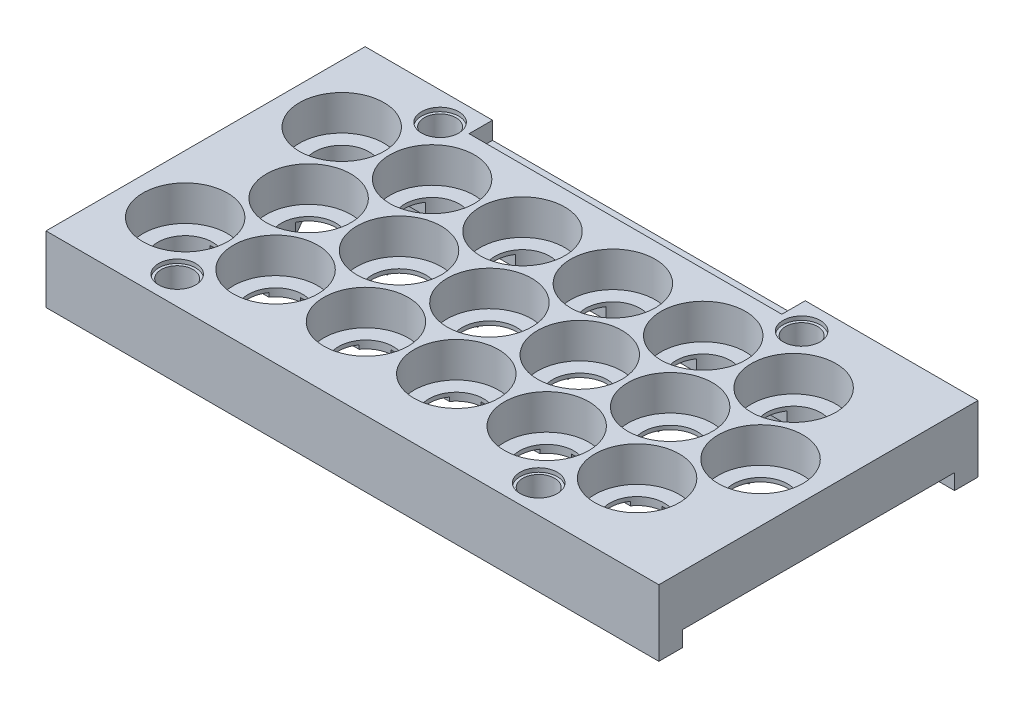
SolidWorks part; units mm, degrees
ref_plane "Front Plane" through (0, 0, 0) normal (0, 0, 1) x (1, 0, 0)
ref_plane "Top Plane" through (0, 0, 0) normal (0, 1, 0) x (1, 0, 0)
ref_plane "Right Plane" through (0, 0, 0) normal (1, 0, 0) x (0, 0, -1)
sketch "Sketch1" plane through (0, 0, 0) normal (0, 1, 0) x (1, 0, 0)
  line L0 (0, 0) -> (11.575, -20.0485) construction
  line L1 (11.575, -20.0485) -> (0, -40.097) construction
  line L2 (0, 0) -> (11.575, 0) construction
  line L3 (11.575, 0) -> (11.575, -20.0485) construction
  line L4 (11.575, -20.0485) -> (11.575, -40.097) construction
  line L5 (11.575, -40.097) -> (0, -40.097) construction
  line L6 (0, 0) -> (23.15, 0) construction
  line L7 (0, 0) -> (23.15, 0) construction
  line L8 (-14.825, -60.922) -> (142.15, -60.922)
  line L9 (-14.825, -60.922) -> (-14.825, 20.825)
  line L10 (-14.825, 20.825) -> (142.15, 20.825)
  line L11 (142.15, -60.922) -> (142.15, 20.825)
  circle A0 centre (0, 0) radius 10.825
  circle A1 centre (11.575, -20.0485) radius 10.825
  circle A2 centre (0, -40.097) radius 10.825
  circle A3 centre (23.15, 0) radius 10.825
  circle A4 centre (34.725, -20.0485) radius 10.825
  circle A5 centre (23.15, -40.097) radius 10.825
  circle A6 centre (46.3, 0) radius 10.825
  circle A7 centre (57.875, -20.0485) radius 10.825
  circle A8 centre (46.3, -40.097) radius 10.825
  circle A9 centre (69.45, 0) radius 10.825
  circle A10 centre (81.025, -20.0485) radius 10.825
  circle A11 centre (69.45, -40.097) radius 10.825
  circle A12 centre (92.6, 0) radius 10.825
  circle A13 centre (104.175, -20.0485) radius 10.825
  circle A14 centre (92.6, -40.097) radius 10.825
  circle A15 centre (115.75, 0) radius 10.825
  circle A16 centre (127.325, -20.0485) radius 10.825
  circle A17 centre (115.75, -40.097) radius 10.825
  circle A18 centre (0, 0) radius 7
  circle A19 centre (11.575, -20.0485) radius 7
  circle A20 centre (0, -40.097) radius 7
  circle A21 centre (23.15, 0) radius 7
  circle A22 centre (34.725, -20.0485) radius 7
  circle A23 centre (23.15, -40.097) radius 7
  circle A24 centre (46.3, 0) radius 7
  circle A25 centre (57.875, -20.0485) radius 7
  circle A26 centre (46.3, -40.097) radius 7
  circle A27 centre (69.45, 0) radius 7
  circle A28 centre (81.025, -20.0485) radius 7
  circle A29 centre (69.45, -40.097) radius 7
  circle A30 centre (92.6, 0) radius 7
  circle A31 centre (104.175, -20.0485) radius 7
  circle A32 centre (92.6, -40.097) radius 7
  circle A33 centre (115.75, 0) radius 7
  circle A34 centre (127.325, -20.0485) radius 7
  circle A35 centre (115.75, -40.097) radius 7
  dimension "D3" = 21.65
  dimension "D11" = 14
  dimension "D1" = 60
  dimension "D2" = 60
  dimension "D4" = 1.5
  dimension "D6" = 23.15
  dimension "D7" = 4
  dimension "D8" = 4
  dimension "D9" = 10
  dimension "D10" = 10
  dimension "D13" = 23.15
  dimension "D5" = 6
  dimension "D12" = 6
extrude "Boss-Extrude2" add sketch "Sketch1" along normal blind 11 contours L8 L11 L10 L9 A17 A16 A15 A14 A13 A12 A11 A10 A9 A8 A7 A6 A5 A4 A3 A2 A1 A0 region at (-13.0551, 0, 20.0485)
extrude "Boss-Extrude3" add sketch "Sketch1<3>" along normal blind 2 contours A0 A18 | A3 A21 | A6 A24 | A9 A27 | A12 A30 | A15 A33 | A1 A19 | A4 A22 | A7 A25 | A10 A28 | A13 A31 | A16 A34 | A17 A35 | A14 A32 | A11 A29 | A8 A26 | A5 A23 | A2 A20 region at (-10.5188, 0, 0) region at (1.0562, 0, 20.0485) region at (-10.5188, 0, 40.097) region at (12.6312, 0, 0) region at (24.2062, 0, 20.0485) region at (12.6312, 0, 40.097) region at (35.7812, 0, 0) region at (47.3562, 0, 20.0485) region at (35.7812, 0, 40.097) region at (58.9312, 0, 0) region at (70.5062, 0, 20.0485) region at (58.9312, 0, 40.097) region at (82.0812, 0, 0) region at (93.6562, 0, 20.0485) region at (82.0812, 0, 40.097) region at (105.2312, 0, 0) region at (116.8062, 0, 20.0485) region at (105.2312, 0, 40.097)
sketch "Sketch1<3>" plane through (0, 0, 0) normal (0, 1, 0) x (1, 0, 0) same geometry as "Sketch1"
sketch "Sketch2" plane through (0, 0, 0) normal (0, -1, 0) x (1, 0, 0)
  line L0 (0, 40.097) -> (11.575, 20.0485) construction
  line L1 (3.4641, 42.097) -> (15.0391, 22.0485)
  line L2 (-3.4641, 38.097) -> (8.1109, 18.0485)
  line L3 (11.575, 20.0485) -> (0, 0) construction
  line L4 (15.0391, 18.0485) -> (3.4641, -2)
  line L5 (8.1109, 22.0485) -> (-3.4641, 2)
  line L6 (19.6859, 38.097) -> (31.2609, 18.0485)
  line L7 (26.6141, 42.097) -> (38.1891, 22.0485)
  line L8 (31.2609, 22.0485) -> (19.6859, 2)
  line L9 (38.1891, 18.0485) -> (26.6141, -2)
  line L10 (23.15, 40.097) -> (34.725, 20.0485) construction
  line L11 (34.725, 20.0485) -> (23.15, 0) construction
  line L12 (42.8359, 38.097) -> (54.4109, 18.0485)
  line L13 (49.7641, 42.097) -> (61.3391, 22.0485)
  line L14 (54.4109, 22.0485) -> (42.8359, 2)
  line L15 (61.3391, 18.0485) -> (49.7641, -2)
  line L16 (46.3, 40.097) -> (57.875, 20.0485) construction
  line L17 (57.875, 20.0485) -> (46.3, 0) construction
  line L18 (65.9859, 38.097) -> (77.5609, 18.0485)
  line L19 (72.9141, 42.097) -> (84.4891, 22.0485)
  line L20 (77.5609, 22.0485) -> (65.9859, 2)
  line L21 (84.4891, 18.0485) -> (72.9141, -2)
  line L22 (69.45, 40.097) -> (81.025, 20.0485) construction
  line L23 (81.025, 20.0485) -> (69.45, 0) construction
  line L24 (89.1359, 38.097) -> (100.7109, 18.0485)
  line L25 (96.0641, 42.097) -> (107.6391, 22.0485)
  line L26 (100.7109, 22.0485) -> (89.1359, 2)
  line L27 (107.6391, 18.0485) -> (96.0641, -2)
  line L28 (92.6, 40.097) -> (104.175, 20.0485) construction
  line L29 (104.175, 20.0485) -> (92.6, 0) construction
  line L30 (112.2859, 38.097) -> (123.8609, 18.0485)
  line L31 (119.2141, 42.097) -> (130.7891, 22.0485)
  line L32 (123.8609, 22.0485) -> (112.2859, 2)
  line L33 (130.7891, 18.0485) -> (119.2141, -2)
  line L34 (115.75, 40.097) -> (127.325, 20.0485) construction
  line L35 (127.325, 20.0485) -> (115.75, 0) construction
  line L36 (-3.4641, 38.097) -> (19.6859, 38.097) construction
  line L37 (0, 40.097) -> (115.75, 40.097) construction
  line L38 (0, 44.097) -> (115.75, 44.097)
  line L39 (0, 36.097) -> (115.75, 36.097)
  line L40 (11.575, 20.0485) -> (127.325, 20.0485) construction
  line L41 (11.575, 24.0485) -> (127.325, 24.0485)
  line L42 (11.575, 16.0485) -> (127.325, 16.0485)
  line L43 (0, 0) -> (115.75, 0) construction
  line L44 (0, 4) -> (115.75, 4)
  line L45 (0, -4) -> (115.75, -4)
  arc A0 (3.4641, 42.097) -> (-3.4641, 38.097) centre (0, 40.097) ccw
  arc A1 (8.1109, 18.0485) -> (15.0391, 22.0485) centre (11.575, 20.0485) ccw
  arc A2 (15.0391, 18.0485) -> (8.1109, 22.0485) centre (11.575, 20.0485) ccw
  arc A3 (-3.4641, 2) -> (3.4641, -2) centre (0, 0) ccw
  arc A4 (26.6141, 42.097) -> (19.6859, 38.097) centre (23.15, 40.097) ccw
  arc A5 (31.2609, 18.0485) -> (38.1891, 22.0485) centre (34.725, 20.0485) ccw
  arc A6 (38.1891, 18.0485) -> (31.2609, 22.0485) centre (34.725, 20.0485) ccw
  arc A7 (19.6859, 2) -> (26.6141, -2) centre (23.15, 0) ccw
  arc A8 (49.7641, 42.097) -> (42.8359, 38.097) centre (46.3, 40.097) ccw
  arc A9 (54.4109, 18.0485) -> (61.3391, 22.0485) centre (57.875, 20.0485) ccw
  arc A10 (61.3391, 18.0485) -> (54.4109, 22.0485) centre (57.875, 20.0485) ccw
  arc A11 (42.8359, 2) -> (49.7641, -2) centre (46.3, 0) ccw
  arc A12 (72.9141, 42.097) -> (65.9859, 38.097) centre (69.45, 40.097) ccw
  arc A13 (77.5609, 18.0485) -> (84.4891, 22.0485) centre (81.025, 20.0485) ccw
  arc A14 (84.4891, 18.0485) -> (77.5609, 22.0485) centre (81.025, 20.0485) ccw
  arc A15 (65.9859, 2) -> (72.9141, -2) centre (69.45, 0) ccw
  arc A16 (96.0641, 42.097) -> (89.1359, 38.097) centre (92.6, 40.097) ccw
  arc A17 (100.7109, 18.0485) -> (107.6391, 22.0485) centre (104.175, 20.0485) ccw
  arc A18 (107.6391, 18.0485) -> (100.7109, 22.0485) centre (104.175, 20.0485) ccw
  arc A19 (89.1359, 2) -> (96.0641, -2) centre (92.6, 0) ccw
  arc A20 (119.2141, 42.097) -> (112.2859, 38.097) centre (115.75, 40.097) ccw
  arc A21 (123.8609, 18.0485) -> (130.7891, 22.0485) centre (127.325, 20.0485) ccw
  arc A22 (130.7891, 18.0485) -> (123.8609, 22.0485) centre (127.325, 20.0485) ccw
  arc A23 (112.2859, 2) -> (119.2141, -2) centre (115.75, 0) ccw
  arc A24 (0, 44.097) -> (0, 36.097) centre (0, 40.097) ccw
  arc A25 (115.75, 36.097) -> (115.75, 44.097) centre (115.75, 40.097) ccw
  arc A26 (11.575, 24.0485) -> (11.575, 16.0485) centre (11.575, 20.0485) ccw
  arc A27 (127.325, 16.0485) -> (127.325, 24.0485) centre (127.325, 20.0485) ccw
  arc A28 (0, 4) -> (0, -4) centre (0, 0) ccw
  arc A29 (115.75, -4) -> (115.75, 4) centre (115.75, 0) ccw
  point P3 (5.7875, 30.0727)
  point P8 (5.7875, 10.0242)
  point P18 (28.9375, 30.0727)
  point P25 (28.9375, 10.0242)
  point P34 (52.0875, 30.0727)
  point P39 (52.0875, 10.0242)
  point P48 (75.2375, 30.0727)
  point P53 (75.2375, 10.0242)
  point P62 (98.3875, 30.0727)
  point P67 (98.3875, 10.0242)
  point P76 (121.5375, 30.0727)
  point P81 (121.5375, 10.0242)
  point P91 (57.875, 40.097)
  point P96 (69.45, 20.0485)
  point P103 (57.875, 0)
  circle M62 centre (0, 0) radius 7
  circle M63 centre (23.15, 0) radius 7
  circle M64 centre (46.3, 0) radius 7
  circle M65 centre (69.45, 0) radius 7
  circle M66 centre (92.6, 0) radius 7
  circle M67 centre (115.75, 0) radius 7
  circle M68 centre (11.575, 20.0485) radius 7
  circle M69 centre (34.725, 20.0485) radius 7
  circle M70 centre (57.875, 20.0485) radius 7
  circle M71 centre (81.025, 20.0485) radius 7
  circle M72 centre (104.175, 20.0485) radius 7
  circle M73 centre (127.325, 20.0485) radius 7
  circle M74 centre (115.75, 40.097) radius 7
  circle M75 centre (92.6, 40.097) radius 7
  circle M76 centre (69.45, 40.097) radius 7
  circle M77 centre (46.3, 40.097) radius 7
  circle M78 centre (23.15, 40.097) radius 7
  circle M79 centre (0, 40.097) radius 7
  dimension "D1" = 8
  dimension "D3" = 23.15
  dimension "D4" = 8
  dimension "D5" = 8
  dimension "D6" = 8
extrude "Cut-Extrude1" cut sketch "Sketch2" against normal blind 1 contours L1 L39 L38 M78 M79 | L7 L39 L38 M77 M78 | L39 L2 L1 M79 M68 | L42 L8 L6 L41 M68 M69 | L6 L41 L7 L39 M69 M78 | L12 L41 L13 L39 M70 M77 | L13 L39 L38 M76 M77 | L18 L41 L19 L39 M71 M76 | L19 L39 L38 M75 M76 | L24 L41 L25 L39 M72 M75 | L25 L39 L38 M74 M75 | L30 L41 L31 M73 M74 | L42 L32 L30 L41 M72 M73 | L42 L26 L24 L41 M71 M72 | L42 L20 L18 L41 M70 M71 | L42 L14 L12 L41 M69 M70 | L45 L44 L4 M62 M63 | L44 L4 L5 M62 M68 | L45 L44 L9 M63 M64 | L45 L44 L15 M64 M65 | L45 L44 L21 M65 M66 | L45 L44 L27 M66 M67 | L44 L27 L42 L26 M66 M72 | L42 L32 L33 M67 M73 | L44 L21 L42 L20 M65 M71 | L44 L15 L42 L14 M64 M70 | L39 L13 M77 | L39 L25 M75 | L39 L19 M76 | L41 L6 M69 | L44 L4 M62 | L44 L15 M64 | L44 L21 M65 | L44 L27 M66 | L41 L30 M73 | L32 L42 M73 | L41 L24 M72 | L26 L42 M72 | L41 L18 M71 | L20 L42 M71 | L41 L12 M70 | L14 L42 M70 | L44 L9 L42 L8 M63 M69 | L8 L42 M69 | L39 L7 M78 | L39 L1 M79 | L44 A29 L45 A28 region at (11.6138, 0, 40.1242) region at (6.3461, 0, 36.4331) region at (5.7834, 0, 30.0255) region at (23.0718, 0, 20.0485) region at (28.9375, 0, 30.0727) region at (34.7638, 0, 40.1242) region at (28.3789, 0, 23.7124) region at (5.7834, 0, 10.0715) region at (29.4961, 0, 36.4331) region at (57.9138, 0, 40.1242) region at (28.3789, 0, 16.3846) region at (28.9375, 0, 10.0242) region at (6.3461, 0, 3.6639) region at (11.6138, 0, -0.0272) region at (52.0875, 0, 30.0727) region at (46.2218, 0, 20.0485) region at (52.6461, 0, 36.4331) region at (81.0638, 0, 40.1242) region at (51.5289, 0, 23.7124) region at (34.7638, 0, -0.0272) region at (75.2375, 0, 30.0727) region at (75.7961, 0, 36.4331) region at (104.2138, 0, 40.1242) region at (74.6789, 0, 23.7124) region at (69.3718, 0, 20.0485) region at (51.5289, 0, 16.3846) region at (52.0875, 0, 10.0242) region at (57.9138, 0, -0.0272) region at (98.3875, 0, 30.0727) region at (98.9461, 0, 36.4331) region at (97.8289, 0, 23.7124) region at (92.5218, 0, 20.0485) region at (74.6789, 0, 16.3846) region at (52.6461, 0, 3.6639) region at (81.0638, 0, -0.0272) region at (121.5416, 0, 30.12) region at (75.2375, 0, 10.0242) region at (120.9789, 0, 23.7124) region at (115.6718, 0, 20.0485) region at (97.8289, 0, 16.3846) region at (75.7961, 0, 3.6639) region at (104.2138, 0, -0.0272) region at (98.3875, 0, 10.0242) region at (121.5416, 0, 9.977) region at (120.9789, 0, 16.3846) region at (98.9461, 0, 3.6639)
sketch "Sketch9" plane through (0, 11, 0) normal (0, 1, 0) x (1, 0, 0)
  line L0 (11.575, -60.922) -> (11.575, 20.825)
  line L1 (-14.825, 20.825) -> (142.15, 20.825) construction
  line L2 (104.175, 20.825) -> (104.175, -60.922)
  line L3 (-14.825, -60.922) -> (142.15, -60.922) construction
  circle A0 centre (11.575, 13.625) radius 4.0767
  circle A1 centre (11.575, -53.722) radius 4.0767
  circle A2 centre (104.175, -53.722) radius 4.0767
  circle A3 centre (104.175, 13.625) radius 4.0767
  point P0 (11.575, 13.625)
  point P7 (11.575, -20.0485)
  point P15 (104.175, -20.0485)
  point P20 (104.175, 13.625)
  point P21 (104.175, -53.722)
  point P22 (11.575, -53.722)
  dimension "D5" = 8.1534
  dimension "D1" = 7.2
  dimension "D4" = 7.2
extrude "Cut-Extrude3" cut sketch "Sketch9" against normal up to next contours A2 | A1 | A0 | A3
sketch "Sketch10" plane through (0, 11, 0) normal (0, 1, 0) x (1, 0, 0)
  circle A0 centre (11.575, 13.625) radius 4.7625
  circle A1 centre (104.175, 13.625) radius 4.7625
  circle A2 centre (104.175, -53.722) radius 4.7625
  circle A3 centre (11.575, -53.722) radius 4.7625
  dimension "D1" = 9.525
extrude "Cut-Extrude4" cut sketch "Sketch10" against normal blind 1
sketch "Sketch13" plane through (0, 0, 0) normal (0, -1, 0) x (1, 0, 0)
  line L0 (142.15, 60.922) -> (142.15, -20.825) construction
  line L5 (3.575, 53.722) -> (3.575, 60.922)
  line L8 (-14.825, 60.922) -> (142.15, 60.922) construction
  line L9 (3.575, 60.922) -> (19.575, 60.922)
  line L10 (19.575, 60.922) -> (19.575, 53.722)
  line L12 (57.875, 20.0485) -> (57.875, -20.825) construction
  line L13 (-14.825, -20.825) -> (142.15, -20.825) construction
  line L14 (11.575, 20.0485) -> (127.325, 20.0485) construction
  line L16 (96.175, 60.922) -> (96.175, 53.722)
  line L17 (112.175, 60.922) -> (96.175, 60.922)
  line L18 (112.175, 53.722) -> (112.175, 60.922)
  line L19 (-14.825, 60.922) -> (142.15, 60.922)
  line L20 (-14.825, 60.922) -> (-14.825, 54.922)
  line L21 (-14.825, 54.922) -> (142.15, 54.922)
  line L22 (142.15, 60.922) -> (142.15, 54.922)
  line L23 (142.15, -20.825) -> (142.15, -14.825)
  line L24 (-14.825, -14.825) -> (142.15, -14.825)
  line L25 (-14.825, -20.825) -> (-14.825, -14.825)
  line L26 (-14.825, -20.825) -> (142.15, -20.825)
  line L27 (112.175, -13.625) -> (112.175, -20.825)
  line L28 (112.175, -20.825) -> (96.175, -20.825)
  line L29 (96.175, -20.825) -> (96.175, -13.625)
  line L32 (19.575, -20.825) -> (19.575, -13.625)
  line L33 (3.575, -20.825) -> (19.575, -20.825)
  line L34 (3.575, -13.625) -> (3.575, -20.825)
  circle A4 centre (11.575, 53.722) radius 6.5
  circle A5 centre (11.575, 53.722) radius 8
  circle A6 centre (104.175, 53.722) radius 8
  circle A7 centre (104.175, 53.722) radius 6.5
  circle A8 centre (104.175, -13.625) radius 6.5
  circle A9 centre (104.175, -13.625) radius 8
  circle A10 centre (11.575, -13.625) radius 8
  circle A11 centre (11.575, -13.625) radius 6.5
  line M15 (142.15, 60.922) -> (-14.825, 60.922)
  line M16 (-14.825, 60.922) -> (-14.825, -20.825)
  line M17 (-14.825, -20.825) -> (142.15, -20.825)
  line M18 (142.15, -20.825) -> (142.15, 60.922)
  dimension "D1" = 13
  dimension "D2" = 16
  dimension "D3" = 6
extrude "Boss-Extrude7" add sketch "Sketch13" along normal blind 6 contours L21 L5 M16 M15 | A5 L5 L21 M15 | A5 L21 L10 M15 | L10 L21 L16 M15 | L21 A5 L19 A4 | A5 L21 A4 | L21 A6 L16 M15 | L21 A7 A6 L19 | L21 A7 A6 | A6 L21 L18 M15 | L18 L21 M18 M15 | A9 L24 L29 L26 | L28 A9 L24 A8 | A9 L26 L27 L24 | L24 L27 L26 M18 | L32 L26 L29 L24 | L24 A9 A8 | L34 L24 M16 M17 | L26 A10 L24 L34 | L24 A11 A10 | L24 A11 A10 L33 | L24 A10 L26 L32 region at (3.7817, 0, 54.3098) region at (-5.625, 0, 57.922) region at (4.8282, 0, 59.2567) region at (5.2714, 0, 58.3681) region at (18.3218, 0, 59.2567) region at (57.875, 0, 57.922) region at (-5.625, 0, -17.825) region at (97.4282, 0, 59.2567) region at (4.8282, 0, -19.1597) region at (96.3817, 0, 54.3098) region at (97.8714, 0, 58.3681) region at (3.7817, 0, -14.2128) region at (4.4261, 0, -14.9942) region at (110.9218, 0, 59.2567) region at (127.1625, 0, 57.922) region at (18.3218, 0, -19.1597) region at (57.875, 0, -17.825) region at (97.4282, 0, -19.1597) region at (127.1625, 0, -17.825) region at (96.3817, 0, -14.2128) region at (97.0261, 0, -14.9942) region at (110.9218, 0, -19.1597)
sketch "Sketch14" plane through (0, 0, 0) normal (0, -1, 0) x (1, 0, 0)
  line L2 (142.15, 54.922) -> (142.15, -14.825) construction
  line L4 (5.2386, 17.0736) -> (-0.5918, 6.9749) construction
  line L5 (5.7446, -4) -> (17.4054, -4) construction
  line L6 (28.8946, -4) -> (40.5554, -4) construction
  line L7 (52.0446, -4) -> (63.7054, -4) construction
  line L8 (75.1946, -4) -> (86.8554, -4) construction
  line L9 (98.3446, -4) -> (110.0054, -4) construction
  line L10 (127.9168, 13.0736) -> (122.0864, 2.9749) construction
  line L11 (122.0864, 37.122) -> (127.9168, 27.0234) construction
  line L12 (98.3446, 44.097) -> (110.0054, 44.097) construction
  line L13 (75.1946, 44.097) -> (86.8554, 44.097) construction
  line L14 (52.0446, 44.097) -> (63.7054, 44.097) construction
  line L15 (28.8946, 44.097) -> (40.5554, 44.097) construction
  line L16 (-0.5918, 33.122) -> (5.2386, 23.0234) construction
  line L17 (5.7446, 44.097) -> (17.4054, 44.097) construction
  line L20 (142.15, 54.922) -> (142.15, -14.825)
  line L22 (5.2386, 17.0736) -> (-0.5918, 6.9749)
  line L23 (5.7446, -4) -> (17.4054, -4)
  line L24 (28.8946, -4) -> (40.5554, -4)
  line L25 (52.0446, -4) -> (63.7054, -4)
  line L26 (75.1946, -4) -> (86.8554, -4)
  line L27 (98.3446, -4) -> (110.0054, -4)
  line L28 (127.9168, 13.0736) -> (122.0864, 2.9749)
  line L29 (122.0864, 37.122) -> (127.9168, 27.0234)
  line L30 (98.3446, 44.097) -> (110.0054, 44.097)
  line L31 (75.1946, 44.097) -> (86.8554, 44.097)
  line L32 (52.0446, 44.097) -> (63.7054, 44.097)
  line L33 (28.8946, 44.097) -> (40.5554, 44.097)
  line L34 (-0.5918, 33.122) -> (5.2386, 23.0234)
  line L35 (5.7446, 44.097) -> (17.4054, 44.097)
  line L36 (112.0845, -14.825) -> (142.15, -14.825) construction
  line L37 (19.4845, -14.825) -> (96.2655, -14.825) construction
  line L38 (-14.825, -14.825) -> (3.6655, -14.825) construction
  line L39 (-14.825, 54.922) -> (-14.825, -14.825) construction
  line L40 (112.0845, 54.922) -> (142.15, 54.922) construction
  line L41 (19.4845, 54.922) -> (96.2655, 54.922) construction
  line L42 (-14.825, 54.922) -> (3.6655, 54.922) construction
  line L43 (112.0845, -14.825) -> (142.15, -14.825)
  line L44 (19.4845, -14.825) -> (96.2655, -14.825)
  line L45 (-14.825, -14.825) -> (3.6655, -14.825)
  line L46 (-14.825, 54.922) -> (-14.825, -14.825)
  line L47 (112.0845, 54.922) -> (142.15, 54.922)
  line L48 (19.4845, 54.922) -> (96.2655, 54.922)
  line L49 (-14.825, 54.922) -> (3.6655, 54.922)
  arc A3 (5.2386, 23.0234) -> (5.2386, 17.0736) centre (11.575, 20.0485) ccw construction
  arc A4 (-0.5918, 6.9749) -> (5.7446, -4) centre (0, 0) ccw construction
  arc A5 (17.4054, -4) -> (28.8946, -4) centre (23.15, 0) ccw construction
  arc A6 (40.5554, -4) -> (52.0446, -4) centre (46.3, 0) ccw construction
  arc A7 (63.7054, -4) -> (75.1946, -4) centre (69.45, 0) ccw construction
  arc A8 (86.8554, -4) -> (98.3446, -4) centre (92.6, 0) ccw construction
  arc A9 (110.0054, -4) -> (122.0864, 2.9749) centre (115.75, 0) ccw construction
  arc A10 (127.9168, 13.0736) -> (127.9168, 27.0234) centre (127.325, 20.0485) ccw construction
  arc A11 (122.0864, 37.122) -> (110.0054, 44.097) centre (115.75, 40.097) ccw construction
  arc A12 (98.3446, 44.097) -> (86.8554, 44.097) centre (92.6, 40.097) ccw construction
  arc A13 (75.1946, 44.097) -> (63.7054, 44.097) centre (69.45, 40.097) ccw construction
  arc A14 (52.0446, 44.097) -> (40.5554, 44.097) centre (46.3, 40.097) ccw construction
  arc A16 (28.8946, 44.097) -> (17.4054, 44.097) centre (23.15, 40.097) ccw construction
  arc A17 (5.7446, 44.097) -> (-0.5918, 33.122) centre (0, 40.097) ccw construction
  arc A21 (5.2386, 23.0234) -> (5.2386, 17.0736) centre (11.575, 20.0485) ccw
  arc A22 (-0.5918, 6.9749) -> (5.7446, -4) centre (0, 0) ccw
  arc A23 (17.4054, -4) -> (28.8946, -4) centre (23.15, 0) ccw
  arc A24 (40.5554, -4) -> (52.0446, -4) centre (46.3, 0) ccw
  arc A25 (63.7054, -4) -> (75.1946, -4) centre (69.45, 0) ccw
  arc A26 (86.8554, -4) -> (98.3446, -4) centre (92.6, 0) ccw
  arc A27 (110.0054, -4) -> (122.0864, 2.9749) centre (115.75, 0) ccw
  arc A28 (127.9168, 13.0736) -> (127.9168, 27.0234) centre (127.325, 20.0485) ccw
  arc A29 (122.0864, 37.122) -> (110.0054, 44.097) centre (115.75, 40.097) ccw
  arc A30 (98.3446, 44.097) -> (86.8554, 44.097) centre (92.6, 40.097) ccw
  arc A31 (75.1946, 44.097) -> (63.7054, 44.097) centre (69.45, 40.097) ccw
  arc A32 (52.0446, 44.097) -> (40.5554, 44.097) centre (46.3, 40.097) ccw
  arc A34 (28.8946, 44.097) -> (17.4054, 44.097) centre (23.15, 40.097) ccw
  arc A35 (5.7446, 44.097) -> (-0.5918, 33.122) centre (0, 40.097) ccw
  arc A36 (112.0845, -14.825) -> (96.2655, -14.825) centre (104.175, -13.625) ccw construction
  arc A37 (19.4845, -14.825) -> (3.6655, -14.825) centre (11.575, -13.625) ccw construction
  arc A38 (96.2655, 54.922) -> (112.0845, 54.922) centre (104.175, 53.722) ccw construction
  arc A39 (3.6655, 54.922) -> (19.4845, 54.922) centre (11.575, 53.722) ccw construction
  arc A40 (112.0845, -14.825) -> (96.2655, -14.825) centre (104.175, -13.625) ccw
  arc A41 (19.4845, -14.825) -> (3.6655, -14.825) centre (11.575, -13.625) ccw
  arc A42 (96.2655, 54.922) -> (112.0845, 54.922) centre (104.175, 53.722) ccw
  arc A43 (3.6655, 54.922) -> (19.4845, 54.922) centre (11.575, 53.722) ccw
extrude "Boss-Extrude9" add sketch "Sketch14" along normal blind 2
sketch "Sketch16" plane through (0, 0, 0) normal (0, -1, 0) x (1, 0, 0)
  line L0 (17.4054, 36.097) -> (12.1668, 27.0234) construction
  line L1 (12.1668, 27.0234) -> (17.3196, 24.0485) construction
  line L2 (17.3196, 24.0485) -> (22.5582, 33.122) construction
  line L3 (22.5582, 33.122) -> (17.4054, 36.097) construction
  line L4 (14.7861, 31.5602) -> (19.9389, 28.5853) construction
  line L5 (15.5361, 32.8592) -> (20.6889, 29.8843)
  line L6 (14.0361, 30.2612) -> (19.1889, 27.2862)
  line L7 (11.575, 20.0485) -> (126.446, 20.0485) construction
  line L8 (40.5554, 36.097) -> (35.3168, 27.0234) construction
  line L9 (35.3168, 27.0234) -> (40.4696, 24.0485) construction
  line L10 (40.4696, 24.0485) -> (45.7082, 33.122) construction
  line L11 (45.7082, 33.122) -> (40.5554, 36.097) construction
  line L12 (37.9361, 31.5602) -> (43.0889, 28.5853) construction
  line L13 (38.6861, 32.8592) -> (43.8389, 29.8843)
  line L14 (37.1861, 30.2612) -> (42.3389, 27.2862)
  line L15 (63.7054, 36.097) -> (58.4668, 27.0234) construction
  line L16 (58.4668, 27.0234) -> (63.6196, 24.0485) construction
  line L17 (63.6196, 24.0485) -> (68.8582, 33.122) construction
  line L18 (68.8582, 33.122) -> (63.7054, 36.097) construction
  line L19 (61.0861, 31.5602) -> (66.2389, 28.5853) construction
  line L20 (61.8361, 32.8592) -> (66.9889, 29.8843)
  line L21 (60.3361, 30.2612) -> (65.4889, 27.2862)
  line L22 (86.8554, 36.097) -> (81.6168, 27.0234) construction
  line L23 (81.6168, 27.0234) -> (86.7696, 24.0485) construction
  line L24 (86.7696, 24.0485) -> (92.0082, 33.122) construction
  line L25 (92.0082, 33.122) -> (86.8554, 36.097) construction
  line L26 (84.2361, 31.5602) -> (89.3889, 28.5853) construction
  line L27 (84.9861, 32.8592) -> (90.1389, 29.8843)
  line L28 (83.4861, 30.2612) -> (88.6389, 27.2862)
  line L29 (110.0054, 36.097) -> (104.7668, 27.0234) construction
  line L30 (104.7668, 27.0234) -> (109.9196, 24.0485) construction
  line L31 (109.9196, 24.0485) -> (115.1582, 33.122) construction
  line L32 (115.1582, 33.122) -> (110.0054, 36.097) construction
  line L33 (107.3861, 31.5602) -> (112.5389, 28.5853) construction
  line L34 (108.1361, 32.8592) -> (113.2889, 29.8843)
  line L35 (106.6361, 30.2612) -> (111.7889, 27.2862)
  line L36 (14.7861, 8.5368) -> (19.9389, 11.5117) construction
  line L37 (15.5361, 7.2377) -> (20.6889, 10.2127)
  line L38 (14.0361, 9.8358) -> (19.1889, 12.8108)
  line L39 (37.9361, 8.5368) -> (43.0889, 11.5117) construction
  line L40 (38.6861, 7.2377) -> (43.8389, 10.2127)
  line L41 (37.1861, 9.8358) -> (42.3389, 12.8108)
  line L42 (61.0861, 8.5368) -> (66.2389, 11.5117) construction
  line L43 (61.8361, 7.2377) -> (66.9889, 10.2127)
  line L44 (60.3361, 9.8358) -> (65.4889, 12.8108)
  line L45 (84.2361, 8.5368) -> (89.3889, 11.5117) construction
  line L46 (84.9861, 7.2377) -> (90.1389, 10.2127)
  line L47 (83.4861, 9.8358) -> (88.6389, 12.8108)
  line L48 (107.3861, 8.5368) -> (112.5389, 11.5117) construction
  line L49 (108.1361, 7.2377) -> (113.2889, 10.2127)
  line L50 (106.6361, 9.8358) -> (111.7889, 12.8108)
  line L51 (115.1582, 6.9749) -> (110.0054, 4) construction
  line L52 (109.9196, 16.0485) -> (115.1582, 6.9749) construction
  line L53 (104.7668, 13.0736) -> (109.9196, 16.0485) construction
  line L54 (110.0054, 4) -> (104.7668, 13.0736) construction
  line L55 (92.0082, 6.9749) -> (86.8554, 4) construction
  line L56 (86.7696, 16.0485) -> (92.0082, 6.9749) construction
  line L57 (81.6168, 13.0736) -> (86.7696, 16.0485) construction
  line L58 (86.8554, 4) -> (81.6168, 13.0736) construction
  line L59 (68.8582, 6.9749) -> (63.7054, 4) construction
  line L60 (63.6196, 16.0485) -> (68.8582, 6.9749) construction
  line L61 (58.4668, 13.0736) -> (63.6196, 16.0485) construction
  line L62 (63.7054, 4) -> (58.4668, 13.0736) construction
  line L63 (45.7082, 6.9749) -> (40.5554, 4) construction
  line L64 (40.4696, 16.0485) -> (45.7082, 6.9749) construction
  line L65 (35.3168, 13.0736) -> (40.4696, 16.0485) construction
  line L66 (40.5554, 4) -> (35.3168, 13.0736) construction
  line L67 (22.5582, 6.9749) -> (17.4054, 4) construction
  line L68 (17.3196, 16.0485) -> (22.5582, 6.9749) construction
  line L69 (12.1668, 13.0736) -> (17.3196, 16.0485) construction
  line L70 (17.4054, 4) -> (12.1668, 13.0736) construction
  arc A0 (15.5361, 32.8592) -> (14.0361, 30.2612) centre (14.7861, 31.5602) ccw
  arc A1 (19.1889, 27.2862) -> (20.6889, 29.8843) centre (19.9389, 28.5853) ccw
  arc A2 (38.6861, 32.8592) -> (37.1861, 30.2612) centre (37.9361, 31.5602) ccw
  arc A3 (42.3389, 27.2862) -> (43.8389, 29.8843) centre (43.0889, 28.5853) ccw
  arc A4 (61.8361, 32.8592) -> (60.3361, 30.2612) centre (61.0861, 31.5602) ccw
  arc A5 (65.4889, 27.2862) -> (66.9889, 29.8843) centre (66.2389, 28.5853) ccw
  arc A6 (84.9861, 32.8592) -> (83.4861, 30.2612) centre (84.2361, 31.5602) ccw
  arc A7 (88.6389, 27.2862) -> (90.1389, 29.8843) centre (89.3889, 28.5853) ccw
  arc A8 (108.1361, 32.8592) -> (106.6361, 30.2612) centre (107.3861, 31.5602) ccw
  arc A9 (111.7889, 27.2862) -> (113.2889, 29.8843) centre (112.5389, 28.5853) ccw
  arc A10 (40.5554, 36.097) -> (45.7082, 33.122) centre (46.3, 40.097) ccw construction
  arc A11 (15.5361, 7.2377) -> (14.0361, 9.8358) centre (14.7861, 8.5368) cw
  arc A12 (19.1889, 12.8108) -> (20.6889, 10.2127) centre (19.9389, 11.5117) cw
  arc A13 (38.6861, 7.2377) -> (37.1861, 9.8358) centre (37.9361, 8.5368) cw
  arc A14 (42.3389, 12.8108) -> (43.8389, 10.2127) centre (43.0889, 11.5117) cw
  arc A15 (61.8361, 7.2377) -> (60.3361, 9.8358) centre (61.0861, 8.5368) cw
  arc A16 (65.4889, 12.8108) -> (66.9889, 10.2127) centre (66.2389, 11.5117) cw
  arc A17 (84.9861, 7.2377) -> (83.4861, 9.8358) centre (84.2361, 8.5368) cw
  arc A18 (88.6389, 12.8108) -> (90.1389, 10.2127) centre (89.3889, 11.5117) cw
  arc A19 (108.1361, 7.2377) -> (106.6361, 9.8358) centre (107.3861, 8.5368) cw
  arc A20 (111.7889, 12.8108) -> (113.2889, 10.2127) centre (112.5389, 11.5117) cw
  point P10 (17.3625, 30.0727)
  point P25 (40.5125, 30.0727)
  point P36 (63.6625, 30.0727)
  point P47 (86.8125, 30.0727)
  point P58 (109.9625, 30.0727)
  point P68 (17.3625, 10.0242)
  point P75 (40.5125, 10.0242)
  point P82 (63.6625, 10.0242)
  point P89 (86.8125, 10.0242)
  point P96 (109.9625, 10.0242)
  dimension "D1" = 1.5
  dimension "D2" = 5
extrude "Boss-Extrude10" add sketch "Sketch16" along normal blind 2
sketch "Sketch17" plane through (0, -2, 0) normal (0, -1, 0) x (-1, 0, 0)
  line L0 (-57.875, -44.097) -> (-57.875, -54.922) construction
  line L1 (-63.7054, -44.097) -> (-52.0446, -44.097) construction
  line L2 (-19.4845, -54.922) -> (-96.2655, -54.922) construction
  line L3 (-142.15, 14.825) -> (-142.15, -54.922) construction
  line L4 (14.825, -54.922) -> (14.825, 14.825) construction
  line L5 (10.825, -49.5095) -> (-57.875, -49.5095) construction
  line L6 (-57.875, -49.5095) -> (-132.15, -49.5095) construction
  line L7 (-127.325, -20.0485) -> (-11.575, -20.0485)
  line L8 (-57.875, 9.4125) -> (-132.15, 9.4125) construction
  line L9 (10.825, 9.4125) -> (-57.875, 9.4125) construction
  line L10 (-57.875, 4) -> (-57.875, 14.825) construction
  circle A0 centre (10.825, -49.5095) radius 2
  circle A1 centre (-57.875, -49.5095) radius 2
  circle A2 centre (-132.15, -49.5095) radius 2
  circle A3 centre (-132.15, 9.4125) radius 2
  circle A4 centre (-57.875, 9.4125) radius 2
  circle A5 centre (10.825, 9.4125) radius 2
  dimension "D1" = 4
  dimension "D2" = 10
  dimension "D3" = 4
extrude "Cut-Extrude5" cut sketch "Sketch17" against normal blind 4 contours A3 | A2 | A4 | A5 | A0 | A1 region at (-10.825, -2, 49.5095) region at (57.875, -2, 49.5095) region at (132.15, -2, 49.5095) region at (132.15, -2, -9.4125) region at (57.875, -2, -9.4125) region at (-10.825, -2, -9.4125)
sketch "Sketch18" plane through (0, 0, -20.825) normal (0, 0, -1) x (-1, 0, 0)
  line L1 (-97.9, 11) -> (-17.8, 11)
  line L2 (-97.9, 11) -> (-17.8, 11)
  line L3 (-97.9, 11) -> (-97.9, 6.525)
  line L4 (-17.8, 11) -> (-17.8, 6.525)
  line L5 (-97.9, 6.525) -> (-17.8, 6.525)
  line L6 (-104.15, 11) -> (-11.55, 11)
  line L7 (14.825, 11) -> (-142.15, 11) construction
  point P0 (-87.2385, 11)
  point P7 (-57.85, 11)
  point P10 (-57.85, 11)
  line M8 (14.825, 11) -> (-142.15, 11)
  dimension "D1" = 80.1
  dimension "D2" = 4.475
  dimension "D3" = 92.6
  dimension "D4" = 38
extrude "Cut-Extrude6" cut sketch "Sketch18" against normal blind 6 contours L3 L5 L4 M8 region at (57.85, 8.7625, -20.825)
sketch "Sketch19" plane through (0, 0, -20.825) normal (0, 0, -1) x (-1, 0, 0)
  line L0 (-85.9, 6.525) -> (-29.8, 6.525)
  line L1 (-85.9, 6.525) -> (-85.9, 0.2625)
  line L2 (-29.8, 6.525) -> (-29.8, 0.2625)
  line L3 (-85.9, 0.2625) -> (-29.8, 0.2625)
  line L4 (-97.9, 6.525) -> (-17.8, 6.525) construction
  line L5 (-97.9, 6.525) -> (-17.8, 6.525) construction
  line L6 (-85.9, 6.525) -> (-97.9, 6.525) construction
  line L7 (-29.8, 6.525) -> (-17.8, 6.525) construction
  line L8 (-57.85, 6.525) -> (-57.85, -6)
  line L9 (14.825, -6) -> (-142.15, -6) construction
  circle A0 centre (-85.9, 0.2625) radius 2
  circle A1 centre (-29.8, 0.2625) radius 2
  point P17 (-57.85, 0.2625)
  dimension "D2" = 4
  dimension "D1" = 12
extrude "Cut-Extrude7" cut sketch "Sketch19" against normal blind 5 contours L1 A0 L3 | L3 A0 L1 | L3 A1 L2 | L2 A1 L3 region at (85.0512, 1.1113, -20.825) region at (86.1829, -0.0204, -20.825) region at (29.5171, -0.0204, -20.825) region at (30.6488, 1.1113, -20.825)
equation "\"hole_diameter\"= 21.65"
equation "\"D3@Sketch1\"=\"hole_diameter\""
equation "\"cell_spacing\"= 1.5"
equation "\"D4@Sketch1\"=\"cell_spacing\""
equation "\"D6@Sketch1\"=\"hole_diameter\"+\"cell_spacing\""
equation "\"len_spacing\"= 4"
equation "\"D7@Sketch1\"=\"len_spacing\""
equation "\"D8@Sketch1\"=\"len_spacing\""
equation "\"wid_spacing\"= 10"
equation "\"D9@Sketch1\"=\"wid_spacing\""
equation "\"D10@Sketch1\"=\"wid_spacing\""
equation "\"nipple\"= 14"
equation "\"D11@Sketch1\"=\"nipple\""
equation "\"D13@Sketch1\"=\"hole_diameter\"+\"cell_spacing\""
equation "\"channel\"= 8"
equation "\"D1@Sketch2\"=\"channel\""
equation "\"D3@Sketch2\"=\"hole_diameter\"+\"cell_spacing\""
equation "\"D4@Sketch2\"=\"channel\""
equation "\"D5@Sketch2\"=\"channel\""
equation "\"D6@Sketch2\"=\"channel\""
equation "\"lip\"= 6"
equation "\"lip_height\"= 1"
equation "\"outer_fillet\"=6"
equation "\"insert_placement\"= 7.2"
equation "\"D4@Sketch9\"=\"insert_placement\""
equation "\"D1@Sketch9\"=\"insert_placement\""
equation "\"heat_insert_diameter\"=8.1534"
equation "\"D5@Sketch9\"=\"heat_insert_diameter\""
equation "\"heat_insert_lip_diameter\"=9.525"
equation "\"D1@Sketch10\"=\"heat_insert_lip_diameter\""
equation "\"bolt_head_diameter\"=13"
equation "\"D1@Sketch13\"=\"bolt_head_diameter\""
equation "\"D2@Sketch13\"=\"bolt_head_diameter\"+3"
equation "\"D3@Sketch13\"=\"lip\""
equation "\"small_heat_insert\"= 4"
equation "\"D1@Sketch17\"=\"small_heat_insert\""
equation "\"bdm_cut_depth\"=6"
equation "\"D1@Cut-Extrude6\"=\"bdm_cut_depth\""
equation "\"D2@Sketch19\"=\"small_heat_insert\""
equation "\"heat_insert_space\"=6"
equation "\"heat_insert\"=5.5"
